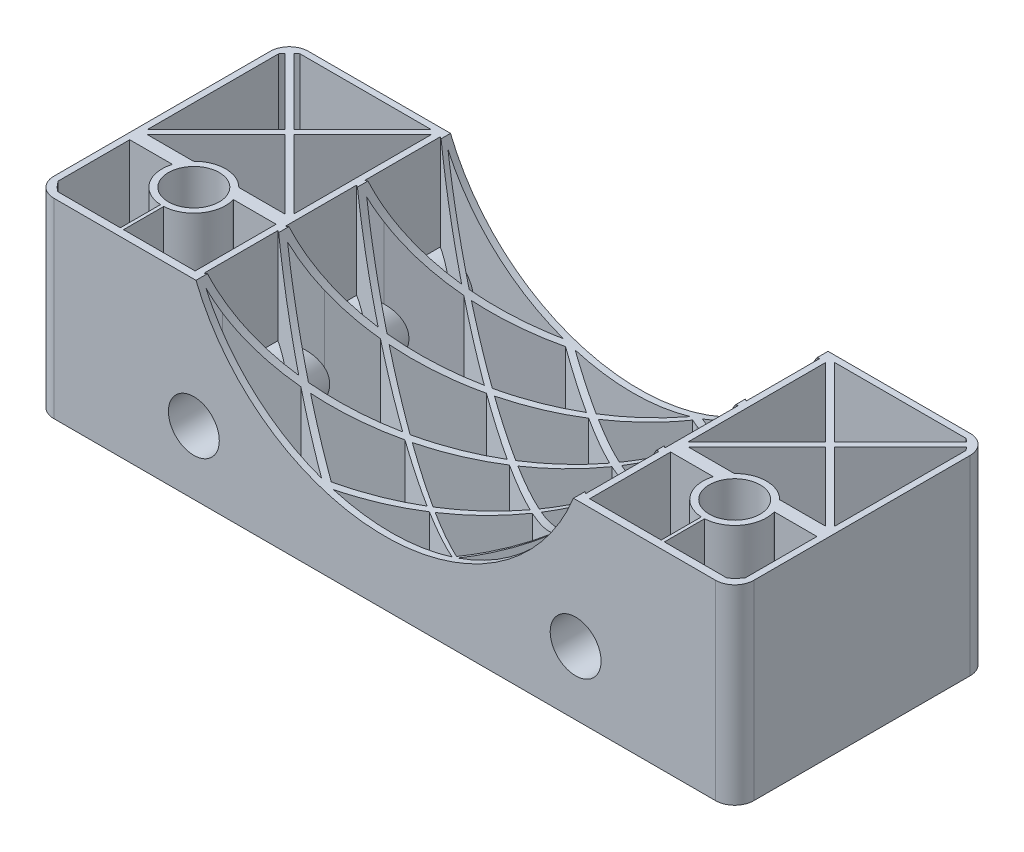
SolidWorks part; units mm, degrees
ref_plane "Front Plane" through (0, 0, 0) normal (0, 0, 1) x (1, 0, 0)
ref_plane "Top Plane" through (0, 0, 0) normal (0, 1, 0) x (1, 0, 0)
ref_plane "Right Plane" through (0, 0, 0) normal (1, 0, 0) x (0, 0, -1)
other "Center of Mass"
ref_plane "Plane1" through (55, 0, 0) normal (1, 0, 0) x (0, 0, -1)
ref_plane "Plane2" through (0, 0, -20) normal (0, 0, 1) x (1, 0, 0)
sketch "Sketch1" plane through (0, 0, 0) normal (0, 1, 0) x (1, 0, 0)
  line L1 (0, 0) -> (110, 0)
  line L2 (0, 0) -> (0, 40)
  line L3 (0, 40) -> (110, 40)
  line L4 (110, 0) -> (110, 40)
  dimension "D1" = 110
  dimension "D2" = 40
extrude "Boss-Extrude1" add sketch "Sketch1" along normal blind 30
sketch "Sketch2" plane through (0, 0, 0) normal (0, 0, 1) x (1, 0, 0)
  line L0 (55, 0) -> (55, 10) construction
  line L1 (0, 0) -> (110, 0) construction
  line L2 (55, 10) -> (55, 42) construction
  circle A0 centre (55, 42) radius 32
  point P5 (55, 0)
  dimension "D1" = 10
  dimension "D2" = 32
extrude "Cut-Extrude1" cut sketch "Sketch2" against normal blind 40
sketch "Sketch3" plane through (0, 0, 0) normal (0, -1, 0) x (1, 0, 0)
  line L0 (110, -20) -> (85, -20) construction
  line L2 (110, 0) -> (110, -40) construction
  line L3 (0, -40) -> (0, 0) construction
  line L4 (0, -20) -> (25, -20) construction
  line L5 (0, -12.5) -> (12.5, -12.5) construction
  line L6 (12.5, -12.5) -> (12.5, 0) construction
  line L7 (0, 0) -> (110, 0) construction
  circle A0 centre (12.5, -12.5) radius 4
  dimension "D5" = 8
  dimension "D1" = 25
  dimension "D2" = 25
  dimension "D3" = 12.5
  dimension "D4" = 12.5
extrude "Cut-Extrude3" cut sketch "Sketch3" against normal blind 30
mirror "Mirror1" about plane through (55, 0, 0) normal (1, 0, 0) of "Cut-Extrude3"
sketch "Sketch7" plane through (0, 0, 0) normal (0, 0, 1) x (1, 0, 0)
  line L2 (55, -16.5) -> (55, 16.5) construction
  circle A2 centre (25, 10) radius 4
  circle A4 centre (85, 10) radius 4
  dimension "D1" = 60
extrude "Cut-Extrude6" cut sketch "Sketch7" against normal blind 40
sketch "Sketch9" plane through (0, 0, 0) normal (0, -1, 0) x (1, 0, 0)
  line L0 (12.5, -12.5) -> (12.5, 0) construction
  line L1 (0, 0) -> (110, 0) construction
  line L2 (12.5, 0) -> (12.5, -40) construction
  line L3 (110, -40) -> (0, -40) construction
  line L4 (1.7071, -39) -> (12.5, -28.2071)
  line L5 (25, 0) -> (25, -40) construction
  line L6 (1.7071, -39) -> (21.7913, -39)
  line L7 (0, -40) -> (0, 0) construction
  line L8 (25, -40) -> (0, -15) construction
  line L9 (0, -15) -> (25, -15) construction
  line L10 (25, -15) -> (0, -40) construction
  line L11 (12.5, -28.2071) -> (23.2929, -39)
  line L12 (23.2929, -39) -> (21.7913, -39)
  line L13 (1, -16.7071) -> (11.7929, -27.5)
  line L14 (1, -38.2929) -> (1, -36.7913)
  line L15 (11.7929, -27.5) -> (1, -38.2929)
  line L16 (1, -16.7071) -> (1, -36.7913)
  line L17 (23.2929, -16) -> (12.5, -26.7929)
  line L19 (12.5, -26.7929) -> (1.7071, -16)
  line L21 (24, -38.2929) -> (13.2071, -27.5)
  line L22 (24, -16.7071) -> (24, -18.2087)
  line L23 (13.2071, -27.5) -> (24, -16.7071)
  line L24 (24, -38.2929) -> (24, -18.2087)
  line L26 (1.7071, -16) -> (8.9293, -16)
  line L27 (23.2929, -16) -> (16.3426, -16) [skipped]
  line L28 (1.7071, -16) -> (3.2087, -16) [skipped]
  line L29 (16.0707, -16) -> (23.2929, -16)
  line L31 (12.25, -1.1996) -> (1, -1.1996)
  line L32 (1, -1.1996) -> (1, -13.9249)
  line L33 (12.25, -1.1996) -> (12.25, -7.5063)
  line L34 (1, -13.9249) -> (7.7073, -13.9249)
  line L35 (7.7073, -13.9249) -> (7.6892, -13.8624)
  line L36 (17.2927, -13.9249) -> (17.3108, -13.8624)
  line L37 (12.75, -1.1996) -> (12.75, -7.5063)
  line L38 (24, -13.9249) -> (17.2927, -13.9249)
  line L39 (24, -1.1996) -> (24, -13.9249)
  line L40 (12.75, -1.1996) -> (24, -1.1996)
  line L41 (55, -16.5) -> (55, 16.5) construction
  line L42 (85, -15) -> (110, -40) construction
  line L43 (110, -15) -> (85, -15) construction
  line L44 (85, -40) -> (110, -15) construction
  line L45 (85, 0) -> (85, -40) construction
  line L46 (97.5, 0) -> (97.5, -40) construction
  line L47 (97.5, -12.5) -> (97.5, 0) construction
  line L48 (97.25, -1.1996) -> (86, -1.1996)
  line L49 (86, -1.1996) -> (86, -13.9249)
  line L50 (86, -13.9249) -> (92.7073, -13.9249)
  line L51 (97.25, -1.1996) -> (97.25, -7.5063)
  line L52 (92.7073, -13.9249) -> (92.6892, -13.8624)
  line L53 (102.2927, -13.9249) -> (102.3108, -13.8624)
  line L54 (109, -13.9249) -> (102.2927, -13.9249)
  line L55 (97.75, -1.1996) -> (97.75, -7.5063)
  line L56 (109, -1.1996) -> (109, -13.9249)
  line L57 (97.75, -1.1996) -> (109, -1.1996)
  line L58 (93.9293, -16) -> (86.7071, -16)
  line L59 (108.2929, -16) -> (101.0707, -16)
  line L60 (86, -38.2929) -> (86, -18.2087)
  line L61 (96.7929, -27.5) -> (86, -16.7071)
  line L62 (86, -16.7071) -> (86, -18.2087)
  line L63 (86, -38.2929) -> (96.7929, -27.5)
  line L64 (97.5, -26.7929) -> (108.2929, -16)
  line L65 (86.7071, -16) -> (97.5, -26.7929)
  line L66 (109, -16.7071) -> (109, -36.7913)
  line L67 (98.2071, -27.5) -> (109, -38.2929)
  line L68 (109, -38.2929) -> (109, -36.7913)
  line L69 (109, -16.7071) -> (98.2071, -27.5)
  line L70 (86.7071, -39) -> (88.2087, -39)
  line L71 (97.5, -28.2071) -> (86.7071, -39)
  line L72 (108.2929, -39) -> (88.2087, -39)
  line L73 (108.2929, -39) -> (97.5, -28.2071)
  circle A1 centre (12.5, -12.5) radius 4 construction
  arc A3 (8.9293, -16) -> (16.0707, -16) centre (12.5, -12.5) ccw
  arc A5 (12.25, -7.5063) -> (7.6892, -13.8624) centre (12.5, -12.5) ccw
  arc A6 (12.75, -7.5063) -> (17.3108, -13.8624) centre (12.5, -12.5) cw
  arc A7 (97.25, -7.5063) -> (92.6892, -13.8624) centre (97.5, -12.5) ccw
  arc A8 (97.75, -7.5063) -> (102.3108, -13.8624) centre (97.5, -12.5) cw
  arc A9 (101.0707, -16) -> (93.9293, -16) centre (97.5, -12.5) cw
  point P18 (12.5, -27.5)
  point P36 (12.5, -27.5)
  point P39 (12.5, -16.5)
  point P40 (10.5635, -16)
  point P41 (14.4365, -16)
  point P50 (8.9293, -16)
  point P52 (12.25, -7.5063)
  point P53 (7.7073, -13.9249)
  point P98 (102.2927, -13.9249)
  point P99 (97.75, -7.5063)
  point P100 (101.0707, -16)
  point P101 (95.5635, -16)
  point P102 (99.4365, -16)
  point P103 (97.5, -16.5)
  point P104 (97.5, -27.5)
  dimension "D5" = 0.5
  dimension "D1" = 12.5
  dimension "D2" = 1
  dimension "D3" = 0.5
  dimension "D4" = 4
extrude "Cut-Extrude7" cut sketch "Sketch9" against normal blind 30
sketch "Sketch11" plane through (0, 0, 0) normal (0, -1, 0) x (1, 0, 0)
  line L0 (25, -1) -> (25, -39) construction
  line L1 (25, -39) -> (85, -39) construction
  line L2 (85, -39) -> (85, -1) construction
  line L3 (85, -1) -> (25, -1) construction
  line L4 (0, 0) -> (110, 0) construction
  line L5 (24, -13.9249) -> (24, -1.1996) construction
  line L6 (110, -40) -> (0, -40) construction
  line L7 (86, -16.7071) -> (86, -38.2929) construction
  line L8 (55, -1) -> (55, -39) construction
  line L9 (25, -20) -> (54, -20) construction
  line L10 (85, -1) -> (65, -1)
  line L11 (65, -1) -> (45, -1)
  line L12 (45, -1) -> (25, -1)
  line L13 (25, -1) -> (25, -13.6)
  line L14 (25, -13.6) -> (25, -26.2)
  line L15 (25, -26.2) -> (25, -39)
  line L16 (85, -39) -> (65, -39)
  line L17 (45, -39) -> (25, -39)
  line L18 (85, -39) -> (25, -39) construction
  line L19 (65, -39) -> (45, -39)
  line L20 (25, -13.8) -> (25, -1)
  line L21 (85, -26.2) -> (85, -39)
  line L22 (85, -1) -> (85, -13.6)
  line L23 (85, -13.6) -> (85, -26.2)
  line L24 (25, -13.8) -> (45, -1) construction
  line L25 (25, -26.2) -> (65, -1) construction
  line L26 (25, -39) -> (85, -1) construction
  line L27 (45, -39) -> (85, -13.6) construction
  line L28 (65, -39) -> (85, -26.2) construction
  line L29 (85, -13.6) -> (65, -1) construction
  line L30 (85, -26.2) -> (45, -1) construction
  line L31 (85, -39) -> (25, -1) construction
  line L32 (65, -39) -> (25, -13.8) construction
  line L33 (25.86, -2.1365) -> (81.8164, -37.5756)
  line L34 (25.9456, -2.1907) -> (25, -1.5918)
  line L35 (81.8164, -37.5756) -> (84.0655, -39)
  line L36 (27.2382, -1.8257) -> (83.9174, -37.7225)
  line L37 (27.5296, -2.0103) -> (25.86, -1)
  line L38 (83.9174, -37.7225) -> (85, -38.4082)
  line L39 (28.4232, -12.2028) -> (38.2658, -5.9035)
  line L40 (38.2658, -5.9035) -> (45.9276, -1)
  line L41 (37.2659, -5.3562) -> (44.0724, -1)
  line L42 (37.2659, -5.3562) -> (27.9267, -11.3333)
  line L43 (27.9267, -11.3333) -> (25, -13.2064)
  line L44 (47.7229, -3.3064) -> (79.6333, -23.4099)
  line L45 (79.6333, -23.4099) -> (85, -26.791)
  line L46 (47.7229, -3.3064) -> (44.0724, -1)
  line L47 (45.9276, -1) -> (81.2018, -23.2162)
  line L48 (81.2018, -23.2162) -> (85, -25.6083)
  line L49 (63.0254, -2.5395) -> (28.312, -24.7044)
  line L50 (28.312, -24.7044) -> (25, -26.8191)
  line L51 (28.3301, -23.5111) -> (61.7814, -2.7322)
  line L52 (61.7814, -2.7322) -> (64.5701, -1)
  line L53 (63.0254, -2.5395) -> (65.4364, -1)
  line L54 (65.4364, -1) -> (69.4058, -3.4802)
  line L55 (69.4058, -3.4802) -> (85, -13.2239)
  line L56 (64.5701, -1) -> (67.6965, -2.9943)
  line L57 (67.6965, -2.9943) -> (85, -14.0318)
  line L58 (85, -14.0318) -> (81.3497, -16.5102)
  line L59 (67.4512, -38.0249) -> (82.2284, -28.5675)
  line L60 (82.2284, -28.5675) -> (85, -26.791)
  line L61 (67.4512, -38.0249) -> (65.9299, -39)
  line L62 (65.9299, -39) -> (29.5093, -16.0499)
  line L63 (29.5093, -16.0499) -> (25, -13.2064)
  line L64 (28.0981, -16.3428) -> (62.6323, -38.0993)
  line L65 (62.6323, -38.0993) -> (64.062, -39)
  line L66 (28.0981, -16.3428) -> (25, -14.391)
  line L67 (28.3301, -23.5111) -> (25, -25.5796)
  line L68 (29.5859, -36.6874) -> (82.8637, -2.9448)
  line L69 (82.8637, -2.9448) -> (85, -1.5918)
  line L70 (78.5744, -4.4777) -> (29.2621, -36.0047)
  line L71 (29.2621, -36.0047) -> (25, -38.7297)
  line L72 (29.5859, -36.6874) -> (25.9345, -39)
  line L73 (47.1403, -38.2332) -> (81.3497, -16.5102)
  line L74 (80.4967, -15.8673) -> (46.2437, -37.6179)
  line L75 (46.2437, -37.6179) -> (44.0673, -39)
  line L76 (80.4967, -15.8673) -> (85, -13.0077)
  line L77 (78.5744, -4.4777) -> (84.014, -1)
  line L78 (47.1403, -38.2332) -> (45.9276, -39)
  line L79 (66.8535, -37.2201) -> (80.6496, -28.3906)
  line L80 (80.6496, -28.3906) -> (85, -25.6083)
  line L81 (66.8535, -37.2201) -> (64.062, -39)
  line L82 (28.4232, -12.2028) -> (25, -14.391)
  line L83 (25, -26.2) -> (45, -39) construction
  line L84 (26.8548, -27.9807) -> (42.5394, -38.0189)
  line L85 (42.5394, -38.0189) -> (44.0673, -39)
  line L86 (26.8548, -27.9807) -> (25, -26.8191)
  line L87 (27.6269, -27.2876) -> (43.5979, -37.5091)
  line L88 (43.5979, -37.5091) -> (45.9276, -39)
  line L89 (27.6269, -27.2876) -> (25, -25.5796)
  point P18 (35, 7.2209)
  point P35 (82.8637, -2.9448)
  point P37 (29.5859, -36.6874)
  point P38 (29.2621, -36.0047)
  point P39 (28.312, -24.7044)
  point P40 (28.3301, -23.5111)
  point P41 (28.0981, -16.3428)
  point P42 (29.5093, -16.0499)
  point P43 (28.4232, -12.2028)
  point P44 (27.9267, -11.3333)
  point P45 (37.2659, -5.3562)
  point P46 (38.2658, -5.9035)
  point P47 (49.0942, -2.9884)
  point P48 (47.7229, -3.3064)
  point P49 (81.2018, -23.2162)
  point P50 (79.6333, -23.4099)
  point P51 (80.6496, -28.3906)
  point P52 (82.2284, -28.5675)
  point P53 (80.4967, -15.8673)
  point P54 (81.3497, -16.5102)
  point P55 (81.5522, -11.1324)
  point P56 (81.3412, -11.8859)
  point P57 (69.4058, -3.4802)
  point P58 (67.6965, -2.9943)
  point P59 (61.7814, -2.7322)
  point P60 (63.0254, -2.5395)
  point P84 (47.1403, -38.2332)
  point P86 (46.2437, -37.6179)
  point P87 (62.6323, -38.0993)
  point P88 (67.4512, -38.0249)
  point P100 (78.5744, -4.4777)
  point P110 (66.8535, -37.2201)
  point P116 (27.6269, -27.2876)
  point P117 (26.8548, -27.9807)
  point P118 (42.5394, -38.0189)
  point P119 (43.5979, -37.5091)
  dimension "D1" = 1
  dimension "D2" = 1
  dimension "D3" = 1
  dimension "D4" = 1
  dimension "D5" = 1
  dimension "D6" = 0.5
  dimension "D7" = 0.5
  dimension "D8" = 0.5
  dimension "D9" = 0.5
  dimension "D10" = 0.5
  dimension "D11" = 0.5
  dimension "D12" = 0.5
  dimension "D13" = 0.5
  dimension "D14" = 0.5
  dimension "D15" = 0.5
  dimension "D16" = 0.5
  dimension "D17" = 0.5
  dimension "D18" = 0.5
  dimension "D19" = 0.5
  dimension "D20" = 0.5
  dimension "D21" = 0.5
  dimension "D22" = 0.5
  dimension "D23" = 0.5
  dimension "D24" = 0.5
  dimension "D25" = 0.5
  dimension "D26" = 0.5
  dimension "D27" = 0.5
  dimension "D28" = 0.5
  dimension "D29" = 0.5
  dimension "D30" = 0.5
  dimension "D31" = 0.5
  dimension "D32" = 0.5
  dimension "D33" = 0.5
  dimension "D34" = 0.5
  dimension "D35" = 0.5
  dimension "D36" = 0.5
  dimension "D37" = 0.5
  dimension "D38" = 0.5
  dimension "D39" = 0.5
  dimension "D40" = 0.5
  dimension "D41" = 0.5
  dimension "D42" = 0.5
extrude "Cut-Extrude9" cut sketch "Sketch11" against normal blind 30 contours L42 L41 L12 L37 L36 | L43 L42 L33 L34 L20 | L39 L82 L63 L62 L51 L33 | L36 L51 L44 L46 L40 L39 | L51 L52 L11 L47 | L67 L51 L64 L66 L14 | L89 L87 L70 L64 L49 L50 | L84 L86 L15 L71 L70 | L85 L84 L68 L72 L17 | L87 L88 L75 L74 L64 L68 | L70 L33 L49 L62 | L70 L44 L49 L36 | L70 L57 L56 L53 L49 L47 | L70 L77 L10 L54 L55 | L55 L76 L22 L69 L68 | L74 L76 L57 L68 L47 | L74 L44 L68 L36 | L74 L33 L68 L62 | L81 L79 L33 L73 L62 | L73 L78 L19 L65 L64 | L79 L80 L45 L44 L73 L36 | L73 L47 L48 L23 L58 | L60 L59 L36 L38 L21 | L59 L61 L16 L35 L33 region at (74.7607, 0, -2.9568) region at (81.9172, 0, -7.419) region at (65.0368, 0, -7.1857) region at (55.2273, 0, -2.9434) region at (75.1028, 0, -13.5666) region at (82.0015, 0, -19.8799) region at (45.0868, 0, -7.3656) region at (54.9723, 0, -13.6251) region at (65.0173, 0, -19.9708) region at (35.0131, 0, -2.9234) region at (74.9895, 0, -26.2724) region at (44.9596, 0, -20.0172) region at (81.9597, 0, -32.6107) region at (54.9667, 0, -26.3397) region at (35.0085, 0, -13.7155) region at (28.0405, 0, -7.389) region at (35.0517, 0, -26.3591) region at (64.9645, 0, -32.658) region at (44.9944, 0, -32.6738) region at (27.9809, 0, -19.9985) region at (74.9809, 0, -37.0754) region at (28.111, 0, -32.765) region at (54.9851, 0, -37.089) region at (35.0189, 0, -37.0753)
sketch "Sketch12" plane through (0, 0, 0) normal (0, 0, 1) x (1, 0, 0)
  line L0 (55, -16.5) -> (55, 16.5) construction
  circle A0 centre (25, 10) radius 5
  circle A1 centre (85, 10) radius 5
  point P0 (25, 10)
  dimension "D1" = 10
extrude "Boss-Extrude3" add sketch "Sketch12" against normal blind 40
sketch "Sketch15" plane through (0, 0, 0) normal (0, 0, 1) x (1, 0, 0)
  line L0 (55, -16.5) -> (55, 16.5) construction
  circle A0 centre (25, 10) radius 4
  circle A1 centre (85, 10) radius 4
  point P0 (25, 10)
  dimension "D1" = 8
extrude "Cut-Extrude10" cut sketch "Sketch15" against normal blind 40
sketch "Sketch16" plane through (0, 30, 0) normal (0, 1, 0) x (1, 0, 0)
  line L0 (104, 0) -> (110, 0)
  line L1 (84.6648, 0) -> (110, 0) construction
  line L2 (110, 0) -> (110, 6)
  line L3 (110, 0) -> (110, 40) construction
  line L4 (-16.5, 20) -> (16.5, 20) construction
  line L5 (110, 40) -> (110, 34)
  line L6 (104, 40) -> (110, 40)
  line L7 (55, -16.5) -> (55, 16.5) construction
  line L8 (6, 40) -> (0, 40)
  line L9 (0, 40) -> (0, 34)
  line L10 (0, 0) -> (0, 6)
  line L11 (6, 0) -> (0, 0)
  arc A0 (110, 6) -> (104, 0) centre (104, 6) cw
  arc A1 (110, 34) -> (104, 40) centre (104, 34) ccw
  arc A2 (0, 34) -> (6, 40) centre (6, 34) cw
  arc A3 (0, 6) -> (6, 0) centre (6, 6) ccw
  dimension "D1" = 6
  dimension "D2" = 6
extrude "Boss-Extrude4" add sketch "Sketch16" against normal blind 30
fillet "Fillet1" radius 3 4 edges at (0, 15, 0) (110, 15, 0) (0, 15, -40) (110, 15, -40)
